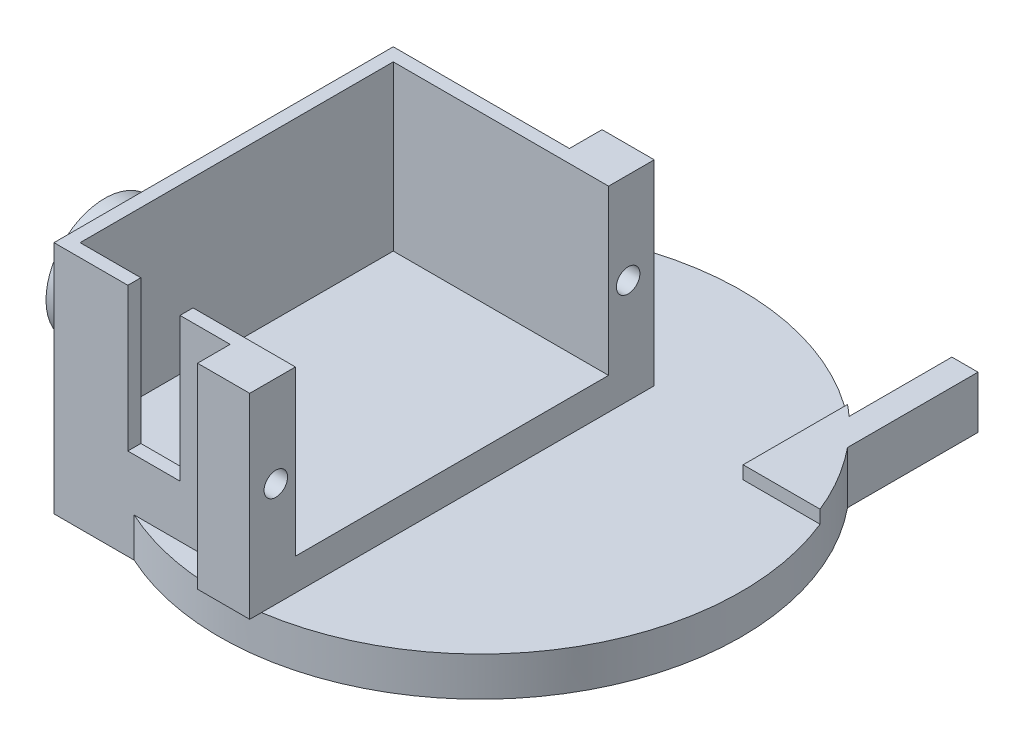
SolidWorks part; units mm, degrees
material "uhlíková ocel 7850"
ref_plane "Přední rovina" through (0, 0, 0) normal (0, 0, 1) x (1, 0, 0)
ref_plane "Horní rovina" through (0, 0, 0) normal (0, 1, 0) x (1, 0, 0)
ref_plane "Pravá rovina" through (0, 0, 0) normal (1, 0, 0) x (0, 0, -1)
sketch "Skica1" plane through (0, 0, 0) normal (0, 1, 0) x (1, 0, 0)
  line L0 (0, -11) -> (0, 11)
  line L1 (0, 11) -> (-3.25, 14.25)
  line L2 (-3.25, 14.25) -> (-30.25, 14.25)
  line L3 (-30.25, 14.25) -> (-30.25, 16.25)
  line L4 (-30.25, 16.25) -> (-2.4216, 16.25)
  line L5 (-2.4216, 16.25) -> (1, 12.8284)
  line L6 (1, 12.8284) -> (1, -12.8284)
  line L7 (1, 0) -> (0, 0) construction
  line L8 (-2.4216, -16.25) -> (1, -12.8284)
  line L9 (-30.25, -16.25) -> (-2.4216, -16.25)
  line L10 (-30.25, -14.25) -> (-30.25, -16.25)
  line L11 (-3.25, -14.25) -> (-30.25, -14.25)
  line L12 (0, -11) -> (-3.25, -14.25)
  dimension "D1" = 11
  dimension "D2" = 135
  dimension "D3" = 27
  dimension "D4" = 1
  dimension "D5" = 2
  dimension "D6" = 2
  dimension "D7" = 14.25
extrude "Přidat vysunutím1" add sketch "Skica1" along normal blind 15
fillet "Zaoblit1" radius 7.5 4 edges at (-30.25, 0, -15.25) (-30.25, 0, 15.25) (-30.25, 15, 15.25) (-30.25, 15, -15.25)
sketch "Skica6" plane through (0, 0, -16.25) normal (0, 0, -1) x (-1, 0, 0)
  circle A0 centre (22.75, 7.5) radius 3.75
  dimension "D1" = 7.5
extrude "Odebrat vysunutím4" cut sketch "Skica6" against normal blind 5
sketch "Skica7" plane through (0, 0, 14.25) normal (0, 0, -1) x (-1, 0, 0)
  circle A0 centre (22.75, 7.5) radius 4.75
  dimension "D1" = 9.5
extrude "Odebrat vysunutím5" cut sketch "Skica7" against normal blind 5
sketch "Skica8" plane through (0, 0, 0) normal (0, -1, 0) x (1, 0, 0)
  line L0 (-2.4216, 16.25) -> (1, 12.8284) construction
  line L1 (0.6569, 13.1716) -> (19, 13.1716)
  line L2 (1, -12.8284) -> (1, 12.8284)
  line L3 (1, -12.8284) -> (19, -12.8284)
  line L4 (19, 13.1716) -> (19, -12.8284)
  line L5 (1, 12.8284) -> (0.6569, 13.1716)
  line L6 (0, -11) -> (0, 11) construction
  line L7 (1, -12.8284) -> (-2.4216, -16.25) construction
  dimension "D1" = 19
  dimension "D2" = 26
extrude "Přidat vysunutím2" add sketch "Skica8" against normal up to surface (15 mm away) up to face at (-8.3619, 15, 0)
sketch "Skica10" plane through (0, 15, 0) normal (0, 1, 0) x (1, 0, 0)
  line L0 (19, -13.1716) -> (19, 12.8284) construction
  line L1 (19, 11.8284) -> (2.5, 11.8284)
  line L2 (19, 11.8284) -> (19, -12.1716)
  line L3 (19, -12.1716) -> (2.5, -12.1716)
  line L4 (2.5, 11.8284) -> (2.5, -12.1716)
  line L6 (0.6569, -13.1716) -> (19, -13.1716) construction
  dimension "D1" = 24
  dimension "D2" = 1
  dimension "D3" = 16.5
extrude "Odebrat vysunutím7" cut sketch "Skica10" against normal blind 14
sketch "Skica11" plane through (19, 0, 0) normal (1, 0, 0) x (0, 0, -1)
  line L0 (-16.25, 0) -> (-13.1716, 0) construction
  line L1 (-13.1716, 15) -> (-15.6716, 15)
  line L2 (-13.1716, 15) -> (-13.1716, 0)
  line L3 (-13.1716, 0) -> (-15.6716, 0)
  line L4 (-15.6716, 15) -> (-15.6716, 0)
  line L5 (12.8284, 0) -> (16.25, 0) construction
  line L6 (12.8284, 15) -> (15.3284, 15)
  line L7 (12.8284, 15) -> (12.8284, 0)
  line L8 (12.8284, 0) -> (15.3284, 0)
  line L9 (15.3284, 15) -> (15.3284, 0)
  dimension "D1" = 2.5
extrude "Přidat vysunutím3" add sketch "Skica11" against normal blind 4
sketch "Skica12" plane through (19, 0, 0) normal (1, 0, 0) x (0, 0, -1)
  line L0 (-13.6716, 8) -> (13.3284, 8) construction
  line L1 (-0.1716, 1) -> (-0.1716, 8) construction
  line L2 (11.8284, 1) -> (-12.1716, 1) construction
  line L3 (-12.1716, 1) -> (-12.1716, 15) construction
  circle A0 centre (-13.6716, 8) radius 0.9
  circle A1 centre (13.3284, 8) radius 0.9
  point P10 (-12.1716, 8)
  dimension "D1" = 1.8
  dimension "D2" = 27
extrude "Odebrat vysunutím8" cut sketch "Skica12" against normal blind 4
sketch "Skica13" plane through (0, 0, 13.1716) normal (0, 0, 1) x (1, 0, 0)
  line L0 (0.6569, 15) -> (15, 15) construction
  line L1 (7.1569, 15) -> (11.1569, 15)
  line L2 (7.1569, 15) -> (7.1569, 4)
  line L3 (7.1569, 4) -> (11.1569, 4)
  line L4 (11.1569, 15) -> (11.1569, 4)
  line L5 (0.6569, 15) -> (0.6569, 0) construction
  dimension "D1" = 4
  dimension "D2" = 11
  dimension "D3" = 6.5
extrude "Odebrat vysunutím9" cut sketch "Skica13" against normal blind 4
sketch "Skica15" plane through (0, 15, 0) normal (0, 1, 0) x (1, 0, 0)
  line L0 (2.5, 11.8284) -> (2.5, -12.1716) construction
  line L1 (-30.25, 16.25) -> (0.5, 16.25)
  line L2 (-30.25, 16.25) -> (-30.25, -16.25)
  line L3 (-30.25, -16.25) -> (0.5, -16.25)
  line L4 (0.5, 16.25) -> (0.5, -16.25)
  dimension "D1" = 2
extrude "Odebrat vysunutím10" cut sketch "Skica15" against normal blind 30
sketch "Skica16" plane through (0, 0, 0) normal (0, -1, 0) x (1, 0, 0)
  line L0 (16, -5) -> (0, -5) construction
  line L1 (0, -5) -> (0, 0) construction
  circle A0 centre (16, -5) radius 20
  dimension "D1" = 40
  dimension "D2" = 16
  dimension "D3" = 5
extrude "Přidat vysunutím4" add sketch "Skica16" along normal blind 3
sketch "Skica17" plane through (0, 15, 0) normal (0, 1, 0) x (1, 0, 0)
  line L1 (0.5, 13.3284) -> (1.5, 13.3284)
  line L2 (0.5, 13.3284) -> (0.5, -14.6716)
  line L3 (0.5, -14.6716) -> (1.5, -14.6716)
  line L4 (1.5, 13.3284) -> (1.5, -14.6716)
  dimension "D1" = 1
  dimension "D2" = 28
extrude "Odebrat vysunutím11" cut sketch "Skica17" against normal up to surface (15 mm away) up to face at (11.9209, 0, -11.728)
sketch "Skica18" plane through (1.5, 0, 0) normal (-1, 0, 0) x (0, 0, 1)
  circle A0 centre (5.7841, 7.9999) radius 6
  dimension "D1" = 12
extrude "Přidat vysunutím5" add sketch "Skica18" along normal blind 0.5
sketch "Skica19" plane through (1, 0, 0) normal (-1, 0, 0) x (0, 0, 1)
  circle A0 centre (5.7841, 7.9999) radius 4.5
  dimension "D1" = 9
extrude "Přidat vysunutím6" add sketch "Skica19" along normal blind 3
sketch "Skica20" plane through (0, 1, 0) normal (0, 1, 0) x (1, 0, 0)
  line L4 (19, -12.1716) -> (19, 11.8284)
  line L5 (19, 11.8284) -> (2.5, 11.8284)
  line L6 (2.5, 11.8284) -> (2.5, -12.1716)
  line L7 (2.5, -12.1716) -> (19, -12.1716)
  line L8 (19, -12.1716) -> (19, 11.8284)
  line L9 (19, 11.8284) -> (2.5, 11.8284)
  line L10 (2.5, 11.8284) -> (2.5, -12.1716)
  line L11 (2.5, -12.1716) -> (19, -12.1716)
  dimension "D1" = 0
extrude "Přidat vysunutím7" add sketch "Skica20" along normal blind 1.44
sketch "Skica21" plane through (0, 0, 0) normal (0, 1, 0) x (1, 0, 0)
  line L1 (29.5, 27.6392) -> (31.5, 27.6392)
  line L2 (29.5, 27.6392) -> (29.5, 19.7564)
  line L4 (31.5, 27.6392) -> (31.5, 17.6392)
  arc A0 (19, -14.7737) -> (1.5, -8.775) centre (16, 5) ccw construction
  arc A1 (31.5, 17.6392) -> (29.5, 19.7564) centre (16, 5) ccw
  dimension "D2" = 13.5
  dimension "D1" = 2
  dimension "D3" = 10
extrude "Přidat vysunutím8" add sketch "Skica21" against normal up to surface (3 mm away) up to face at (16, -3, -25)
sketch "Skica22" plane through (0, 0, 0) normal (0, 1, 0) x (1, 0, 0)
  line L0 (29.5, 27.6392) -> (31.5, 27.6392)
  line L1 (31.5, 27.6392) -> (31.5, 17.6392)
  line L2 (29.5, 27.6392) -> (29.5, 19.7564)
  line L3 (34.5429, 12.4941) -> (28.6464, 12.4941)
  line L4 (28.6464, 12.4941) -> (28.6464, 20.4941)
  arc A0 (29.5, 19.7564) -> (28.6464, 20.4941) centre (16, 5) ccw
  arc A1 (29.5, 19.7564) -> (1.5, -8.775) centre (16, 5) ccw construction
  arc A2 (31.5, 17.6392) -> (34.5429, 12.4941) centre (16, 5) cw
  arc A3 (19, -14.7737) -> (31.5, 17.6392) centre (16, 5) ccw construction
  dimension "D1" = 6
  dimension "D2" = 8
extrude "Přidat vysunutím9" add sketch "Skica22" along normal blind 1
sketch "Skica23" plane through (0, 0, 0) normal (0, -1, 0) x (1, 0, 0)
  line L0 (1.5, 8.775) -> (1.5, 13.1716)
  line L1 (1.5, 13.1716) -> (7.6457, 13.1716)
  arc A1 (31.5, -17.6392) -> (29.5, -19.7564) centre (16, -5) ccw construction
  arc A2 (7.6457, 13.1716) -> (1.5, 8.775) centre (16, -5) ccw
extrude "Přidat vysunutím10" add sketch "Skica23" along normal up to surface (3 mm away) up to face at (23.2404, -3, -16.3105)
sketch "Skica24" plane through (0, -3, 0) normal (0, -1, 0) x (1, 0, 0)
  circle A0 centre (16, -5) radius 1
  dimension "D1" = 2
extrude "Odebrat vysunutím12" cut sketch "Skica24" against normal blind 0.5 contours A0
sketch "Skica25" plane through (0, -3, 0) normal (0, -1, 0) x (1, 0, 0)
  line L1 (15, -17.5) -> (17, -17.5)
  line L2 (15, -17.5) -> (15, 7.5)
  line L3 (15, 7.5) -> (17, 7.5)
  line L4 (17, -17.5) -> (17, 7.5)
  line L5 (15, -17.5) -> (17, 7.5) construction
  line L6 (15, 7.5) -> (17, -17.5) construction
  line L7 (28.5, -6) -> (3.5, -6)
  line L8 (28.5, -6) -> (28.5, -4)
  line L9 (28.5, -4) -> (3.5, -4)
  line L10 (3.5, -6) -> (3.5, -4)
  line L11 (28.5, -6) -> (3.5, -4) construction
  line L12 (28.5, -4) -> (3.5, -6) construction
  circle A0 centre (16, -5) radius 1 construction
  circle A1 centre (16, -5) radius 1 construction
  point P0 (16, -5)
  point P6 (16, -5)
  circle M1 centre (16, -5) radius 1
  dimension "D1" = 25
extrude "Odebrat vysunutím14" cut sketch "Skica25" against normal blind 0.5 contours L9 L4 L3 L2 | L10 L7 L2 L9 | L8 L9 L4 L7 | L4 L7 L2 L1 | L9 L2 M1 | L4 L9 M1 | L7 L4 M1 | L7 L2 M1 region at (16, -3, -11.75) region at (9.25, -3, -5) region at (15.2234, -3, -5.7766) region at (16.7766, -3, -5.7766) region at (22.75, -3, -5) region at (15.2234, -3, -4.2234) region at (16.7766, -3, -4.2234) region at (16, -3, 1.75)
